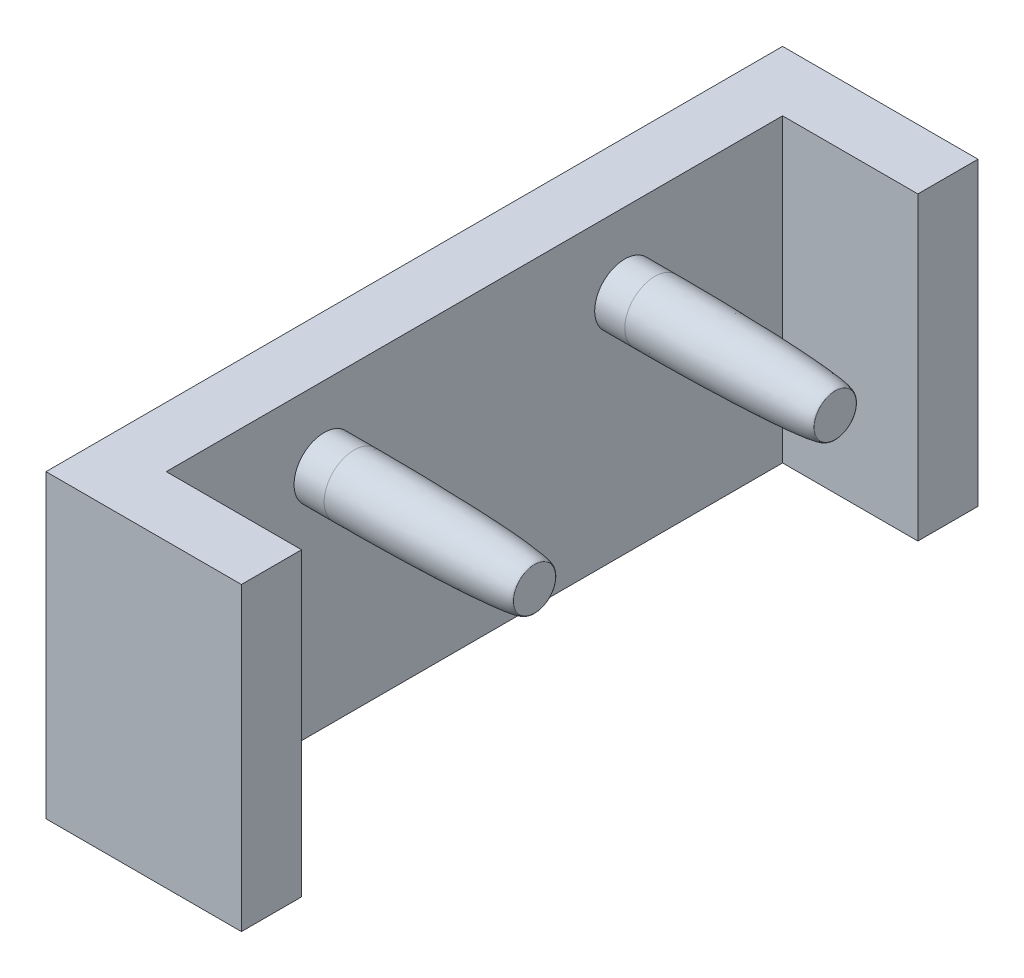
SolidWorks part; units mm, degrees
ref_plane "Front Plane" through (0, 0, 0) normal (0, 0, 1) x (1, 0, 0)
ref_plane "Top Plane" through (0, 0, 0) normal (0, 1, 0) x (1, 0, 0)
ref_plane "Right Plane" through (0, 0, 0) normal (1, 0, 0) x (0, 0, -1)
sketch "Sketch1" plane through (0, 0, 0) normal (1, 0, 0) x (0, 0, -1)
  line L0 (-5, 0) -> (5, 0) construction
  circle A0 centre (-5, 0) radius 1
  circle A1 centre (5, 0) radius 1
  point P4 (0, 0)
  dimension "D2" = 2
  dimension "D1" = 10
extrude "Boss-Extrude1" add sketch "Sketch1" along normal blind 7
sketch "Sketch2" plane through (0, 0, 0) normal (-1, 0, 0) x (0, 0, 1)
  line L1 (-10.25, 2.5) -> (10.25, 2.5)
  line L2 (-10.25, 2.5) -> (-10.25, -7.5)
  line L3 (-10.25, -7.5) -> (10.25, -7.5)
  line L4 (10.25, 2.5) -> (10.25, -7.5)
  line L5 (-10.25, 2.5) -> (10.25, -7.5) construction
  line L6 (-10.25, -7.5) -> (10.25, 2.5) construction
  line L7 (0, 0) -> (0, -2.5) construction
  circle A1 centre (-5, 0) radius 1
  circle A2 centre (-5, 0) radius 1 construction
  point P0 (0, 0)
  point P5 (0, 0)
  point P6 (0, 0)
  dimension "D4" = 2.5
  dimension "D1" = 20.5
  dimension "D2" = 10
  dimension "D3" = 0
extrude "Boss-Extrude2" add sketch "Sketch2" along normal blind 2
sketch "Sketch4" plane through (-2, 0, 0) normal (-1, 0, 0) x (0, 0, 1)
  line L0 (-10.25, -7.5) -> (10.25, -7.5) construction
  line L1 (-12.25, -7.5) -> (12.25, -7.5) construction
  line L2 (-12.25, -7.5) -> (-12.25, 2.5)
  line L3 (-12.25, 2.5) -> (12.25, 2.5) construction
  line L4 (12.25, -7.5) -> (12.25, 2.5)
  line L5 (-10.25, 2.5) -> (-10.25, -7.5) construction
  line L6 (10.25, -7.5) -> (10.25, 2.5) construction
  line L7 (10.25, 2.5) -> (-10.25, 2.5) construction
  line L8 (-12.25, 2.5) -> (-10.25, 2.5)
  line L9 (-10.25, 2.5) -> (-10.25, -7.5)
  line L10 (-10.25, -7.5) -> (-12.25, -7.5)
  line L11 (10.25, 2.5) -> (12.25, 2.5)
  line L12 (12.25, -7.5) -> (10.25, -7.5)
  line L13 (10.25, -7.5) -> (10.25, 2.5)
  dimension "D1" = 2
  dimension "D2" = 2
extrude "Boss-Extrude3" add sketch "Sketch4" against normal blind 6.5
fillet "Fillet1" radius 6 2 edges at (7, 0, -6) (7, 0, 4) second distance 0.3 first distance on face at (7, 0, -6) first distance on face at (7, 0, 4)
